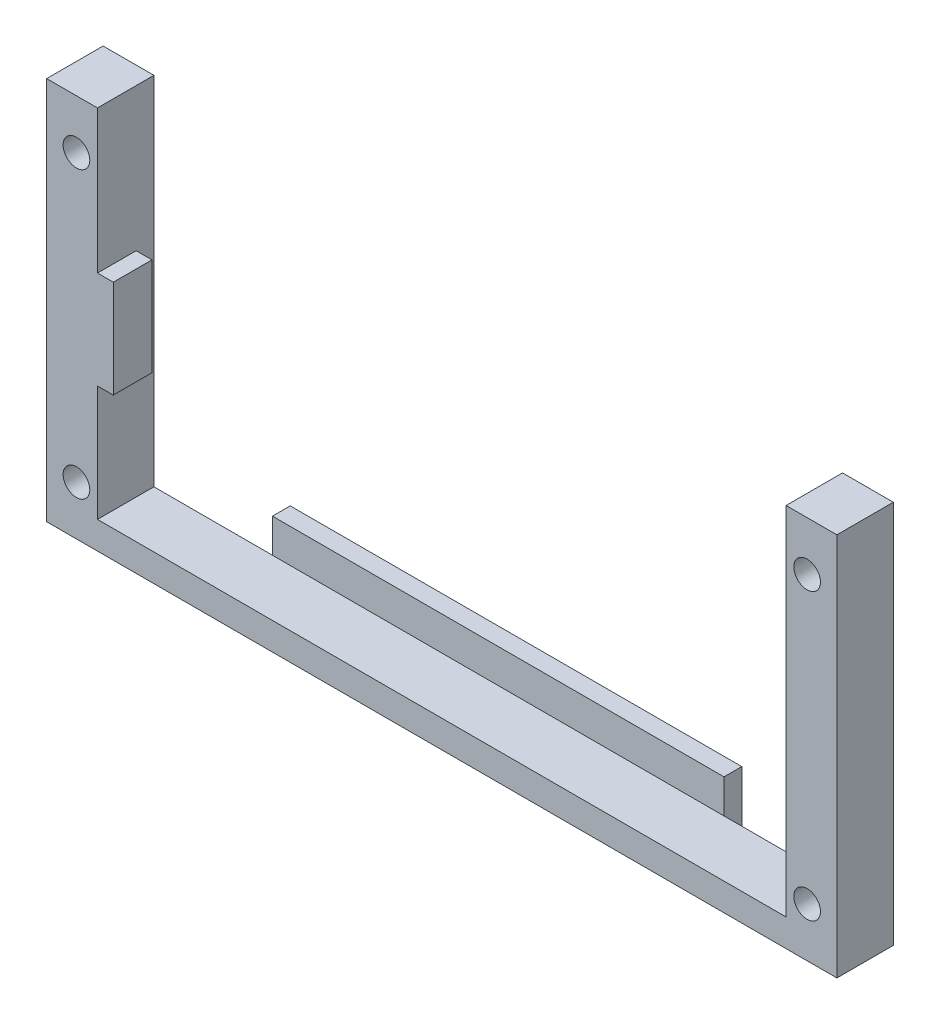
SolidWorks part; units mm, degrees
ref_plane "Front Plane" through (0, 0, 0) normal (0, 0, 1) x (1, 0, 0)
ref_plane "Top Plane" through (0, 0, 0) normal (0, 1, 0) x (1, 0, 0)
ref_plane "Right Plane" through (0, 0, 0) normal (1, 0, 0) x (0, 0, -1)
sketch "Sketch1" plane through (0, 0, 0) normal (0, 0, 1) x (1, 0, 0)
  line L1 (-44.45, 21.59) -> (44.45, 21.59)
  line L2 (-44.45, 21.59) -> (-44.45, -21.59)
  line L3 (-44.45, -21.59) -> (44.45, -21.59)
  line L4 (44.45, 21.59) -> (44.45, -21.59)
  line L5 (-38.735, 18.5) -> (38.735, 18.5)
  line L6 (-38.735, 18.5) -> (-38.735, -18.5)
  line L7 (-38.735, -18.5) -> (38.735, -18.5)
  line L8 (38.735, 18.5) -> (38.735, -18.5)
  point P4 (0, 21.59)
  point P5 (-44.45, 0)
  point P11 (0, 18.5)
  point P12 (-38.735, 0)
  dimension "D1" = 88.9
  dimension "D2" = 43.18
  dimension "D3" = 77.47
  dimension "D4" = 37
extrude "Boss-Extrude1" add sketch "Sketch1" along normal blind 6.35
sketch "Sketch2" plane through (0, 0, 6.35) normal (0, 0, 1) x (1, 0, 0)
  line L2 (0, -55) -> (0, 55) construction
  line L4 (55, 0) -> (-55, 0) construction
  circle A1 centre (41.1, 16.05) radius 1.5
  circle A2 centre (-41.1, 16.05) radius 1.5
  circle A3 centre (-41.1, -16.05) radius 1.5
  circle A4 centre (41.1, -16.05) radius 1.5
  dimension "D1" = 82.2
  dimension "D3" = 3
  dimension "D2" = 32.1
extrude "Cut-Extrude1" cut sketch "Sketch2" against normal blind 10.16
sketch "Sketch4" plane through (-38.735, 0, 0) normal (1, 0, 0) x (0, 0, -1)
  line L0 (-6.35, -21.59) -> (-6.35, 21.59) construction
  line L1 (-6.35, 5.5) -> (-2, 5.5)
  line L2 (-6.35, 5.5) -> (-6.35, -5.5)
  line L3 (-6.35, -5.5) -> (-2, -5.5)
  line L4 (-2, 5.5) -> (-2, -5.5)
  point P6 (-2, 0)
  dimension "D1" = 11
  dimension "D2" = 4.35
extrude "Boss-Extrude3" add sketch "Sketch4" along normal blind 1.778
sketch "Sketch5" plane through (0, 0, 0) normal (0, 0, -1) x (-1, 0, 0)
  line L0 (-44.45, 21.59) -> (44.45, 21.59) construction
  line L1 (-38.735, 21.59) -> (38.735, 21.59)
  line L2 (-38.735, 21.59) -> (-38.735, 18.5)
  line L3 (-38.735, 18.5) -> (38.735, 18.5)
  line L4 (38.735, 21.59) -> (38.735, 18.5)
extrude "Cut-Extrude2" cut sketch "Sketch5" against normal through all
sketch "Sketch6" plane through (0, 0, 0) normal (0, 0, -1) x (-1, 0, 0)
  line L0 (38.735, -18.5) -> (-38.735, -18.5) construction
  line L1 (-25.4, -18.5) -> (25.4, -18.5)
  line L2 (-25.4, -18.5) -> (-25.4, -21.59)
  line L3 (-25.4, -21.59) -> (25.4, -21.59)
  line L4 (25.4, -18.5) -> (25.4, -21.59)
  line L5 (44.45, -21.59) -> (-44.45, -21.59) construction
  point P8 (0, -18.5)
  dimension "D1" = 50.8
extrude "Boss-Extrude4" add sketch "Sketch6" along normal blind 2
sketch "Sketch7" plane through (0, -18.5, 0) normal (0, 1, 0) x (1, 0, 0)
  line L1 (-25.4, 2) -> (25.4, 2)
  line L2 (-25.4, 2) -> (-25.4, 0)
  line L3 (-25.4, 0) -> (25.4, 0)
  line L4 (25.4, 2) -> (25.4, 0)
extrude "Boss-Extrude5" add sketch "Sketch7" along normal blind 3.81
